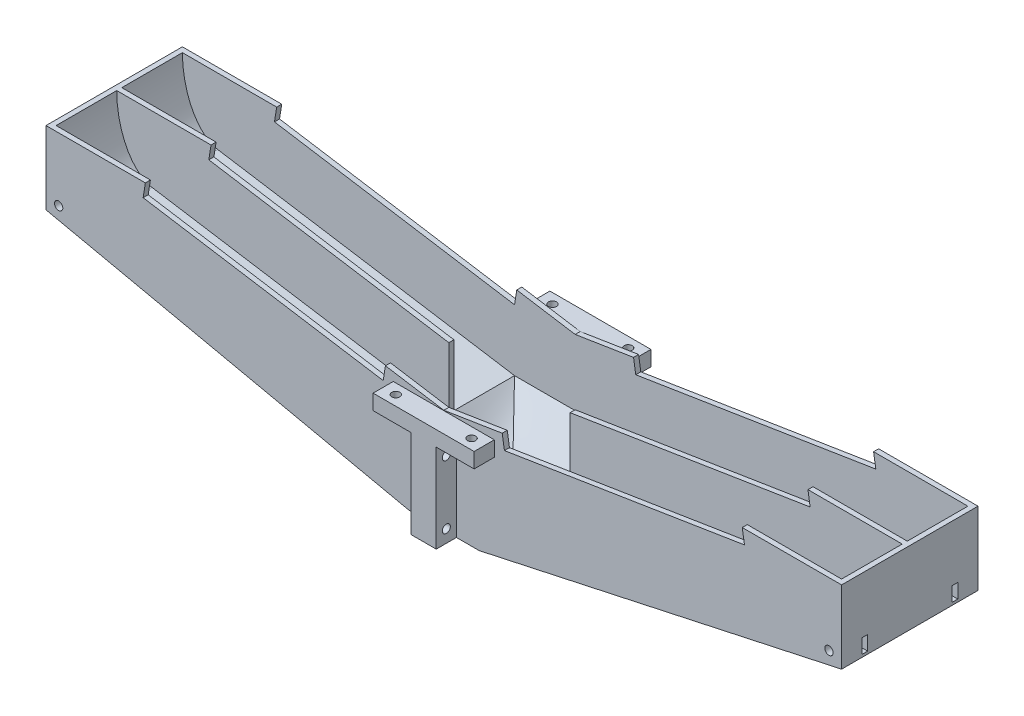
SolidWorks part; units mm, degrees
ref_plane "Front Plane" through (0, 0, 0) normal (0, 0, 1) x (1, 0, 0)
ref_plane "Top Plane" through (0, 0, 0) normal (0, 1, 0) x (1, 0, 0)
ref_plane "Right Plane" through (0, 0, 0) normal (1, 0, 0) x (0, 0, -1)
sketch "Sketch1" plane through (0, 0, 0) normal (0, 1, 0) x (1, 0, 0)
  line L1 (-157.5, -27) -> (157.5, -27)
  line L2 (-157.5, -27) -> (-157.5, 27)
  line L3 (-157.5, 27) -> (157.5, 27)
  line L4 (157.5, -27) -> (157.5, 27)
  line L5 (-157.5, -27) -> (157.5, 27) construction
  line L6 (-157.5, 27) -> (157.5, -27) construction
  point P0 (0, 0)
  dimension "D2" = 315
  dimension "D1" = 54
extrude "Boss-Extrude2" add sketch "Sketch1" along normal blind 60
sketch "Sketch7" plane through (0, 0, 0) normal (0, 0, 1) x (1, 0, 0)
  line L0 (-155.5, 60) -> (-155.5, 36) construction
  line L1 (-141.5, 33.7643) -> (-24, 15)
  line L2 (-157.5, 60) -> (157.5, 60) construction
  line L3 (141.5, 33.7643) -> (24, 15)
  line L4 (-155.5, 36) -> (0, 11.1673) construction
  line L5 (0, 11.1673) -> (155.5, 36) construction
  line L6 (155.5, 36) -> (155.5, 60) construction
  line L7 (155.5, 60) -> (-155.5, 60)
  line L8 (-157.5, 60) -> (-157.5, 0) construction
  line L9 (157.5, 60) -> (157.5, 0) construction
  line L10 (0, 60) -> (0, 0) construction
  line L12 (-24, 15) -> (24, 15)
  line L13 (-157.5, 0) -> (157.5, 0) construction
  ellipse E0 centre (-140.0618, 60) end of major axis (-140.0618, 33.6497) minor radius 15.4382 (-141.5, 33.7643) -> (-155.5, 60) cw
  ellipse E1 centre (140.0618, 60) end of major axis (140.0618, 86.3503) minor radius 15.4382 (155.5, 60) -> (141.5, 33.7643) cw
  dimension "D1" = 2
  dimension "D2" = 2
  dimension "D3" = 24
  dimension "D4" = 15
  dimension "D5" = 48
  dimension "D6" = 16
extrude "Cut-Extrude2" cut sketch "Sketch7" along normal offset from surface 2 and the other way offset from surface 2 up to face at (0, 30, 27) other way up to face at (0, 30, -27)
extrude "Boss-Extrude3" add sketch "Sketch7<2>" along normal mid plane 2
sketch "Sketch7<2>" plane through (0, 0, 0) normal (0, 0, 1) x (1, 0, 0) same geometry as "Sketch7"
sketch "Sketch9" plane through (0, 15, 0) normal (0, 1, 0) x (1, 0, 0)
  line L1 (-24, -25) -> (24, -25)
  line L2 (-24, -25) -> (-24, 25)
  line L3 (-24, 25) -> (24, 25)
  line L4 (24, -25) -> (24, 25)
  line L5 (-24, -25) -> (24, 25) construction
  line L6 (-24, 25) -> (24, -25) construction
  point P0 (0, 0)
extrude "Cut-Extrude5" cut sketch "Sketch9" along normal through all
sketch "Sketch10" plane through (0, 0, 0) normal (0, -1, 0) x (1, 0, 0)
  circle A0 centre (0, 0) radius 12
  dimension "D1" = 24
extrude "Cut-Extrude6" cut sketch "Sketch10" against normal blind 2
sketch "Sketch4" plane through (0, 2, 0) normal (0, -1, 0) x (1, 0, 0)
  circle A0 centre (0, 0) radius 12
  dimension "D1" = 24
loft "Cut-Loft3" cut profiles "Sketch4", "Sketch9<2>" connector at (0, 2, -12) connector at (-24, 15, -25)
sketch "Sketch9<2>" plane through (0, 15, 0) normal (0, 1, 0) x (1, 0, 0) same geometry as "Sketch9"
sketch "Sketch11" plane through (0, 0, 27) normal (0, 0, 1) x (1, 0, 0)
  line L0 (-157.5, 31.0917) -> (-14, 0)
  line L1 (-157.5, 60) -> (-157.5, 0) construction
  line L2 (-157.5, 0) -> (157.5, 0) construction
  line L3 (-14, 0) -> (-157.5, 0)
  line L4 (-157.5, 0) -> (-157.5, 31.0917)
  line L5 (157.5, 31.0917) -> (157.5, 0)
  line L6 (157.5, 60) -> (157.5, 0) construction
  line L7 (157.5, 0) -> (14, 0)
  line L8 (14, 0) -> (157.5, 31.0917)
  line L9 (-118.1608, 60) -> (-119.042, 54.4819)
  line L10 (-24, 60) -> (-155.5, 60) construction
  line L11 (-119.042, 54.4819) -> (-24, 39.3041)
  line L12 (-118.1608, 60) -> (118.1608, 60)
  line L13 (155.5, 60) -> (24, 60) construction
  line L14 (-141.5, 33.7643) -> (-24, 15) construction
  line L15 (0, 60) -> (0, 0) construction
  line L16 (-141.5, 33.7643) -> (-24, 15) construction
  line L17 (118.1608, 60) -> (119.042, 54.4819)
  line L18 (119.042, 54.4819) -> (24, 39.3041)
  line L19 (-24, 39.3041) -> (-23.1188, 44.8222)
  line L20 (-23.1188, 44.8222) -> (0, 41.1302)
  line L21 (0, 41.1302) -> (23.1188, 44.8222)
  line L22 (23.1188, 44.8222) -> (24, 39.3041)
  line L23 (-24, 60) -> (-24, 15) construction
  line L24 (-12, 0) -> (12, 0) construction
  line L25 (-12, 0) -> (12, 0) construction
  line L26 (-141.5, 33.7643) -> (-142.7705, 27.9003) construction
  line L27 (-152.5, 35) -> (152.5, 35) construction
  line L28 (-157.5, 60) -> (-157.5, 0) construction
  circle A0 centre (-152.5, 35) radius 1.65
  circle A1 centre (152.5, 35) radius 1.65
  point P45 (0, 35)
  dimension "D5" = 3.3
  dimension "D1" = 6
  dimension "D2" = 2
  dimension "D3" = 24
  dimension "D4" = 5.588
  dimension "D6" = 25
  dimension "D7" = 5
extrude "Cut-Extrude7" cut sketch "Sketch11" against normal through all
ref_plane "Plane1" through (0, 0, 19) normal (0, 0, 1) x (1, 0, 0)
sketch "Sketch12" plane through (0, 0, 19) normal (0, 0, 1) x (1, 0, 0)
  line L0 (-157.5, 60) -> (-157.5, 31.0917) construction
  line L1 (-150.8546, 37.85) -> (-157.5, 37.85)
  line L2 (-157.5, 37.85) -> (-157.5, 32.15)
  line L3 (157.5, 37.85) -> (157.5, 32.15)
  line L4 (-157.5, 32.15) -> (-150.8546, 32.15)
  line L5 (-150.8546, 32.15) -> (-149.2091, 35)
  line L6 (-149.2091, 35) -> (-150.8546, 37.85)
  line L7 (150.8546, 37.85) -> (149.2091, 35)
  line L8 (149.2091, 35) -> (150.8546, 32.15)
  line L9 (150.8546, 32.15) -> (157.5, 32.15)
  line L10 (157.5, 60) -> (157.5, 31.0917) construction
  line L12 (157.5, 37.85) -> (150.8546, 37.85)
  line L13 (-153.7857, 38.4731) -> (-155.104, 36.1897) [skipped]
  line L14 (-156.1507, 35.6231) -> (-154.8323, 33.3397) [skipped]
  line L15 (156.3932, 33.9568) -> (154.9682, 36.425) [skipped]
  line L16 (154.1454, 32.15) -> (154.9682, 33.575) [skipped]
  circle A0 centre (-152.5, 35) radius 2.85 construction
  circle A1 centre (152.5, 35) radius 2.85 construction
  dimension "D1" = 5.7
extrude "Cut-Extrude8" cut sketch "Sketch12" against normal blind 2.3
ref_plane "Plane2" through (0, 0, -19) normal (0, 0, -1) x (-1, 0, 0)
sketch "Sketch13" plane through (0, 0, -19) normal (0, 0, -1) x (-1, 0, 0)
  line L1 (-150.8546, 37.85) -> (-157.5, 37.85)
  line L2 (-157.5, 37.85) -> (-157.5, 32.15)
  line L3 (157.5, 37.85) -> (157.5, 32.15)
  line L4 (-157.5, 32.15) -> (-150.8546, 32.15)
  line L5 (-150.8546, 32.15) -> (-149.2091, 35)
  line L6 (-149.2091, 35) -> (-150.8546, 37.85)
  line L7 (150.8546, 37.85) -> (149.2091, 35)
  line L8 (149.2091, 35) -> (150.8546, 32.15)
  line L9 (150.8546, 32.15) -> (157.5, 32.15)
  line L11 (157.5, 60) -> (157.5, 31.0917) construction
  line L12 (157.5, 37.85) -> (150.8546, 37.85)
  line L13 (-153.7857, 38.4731) -> (-155.104, 36.1897) [skipped]
  line L14 (-156.1507, 35.6231) -> (-154.8323, 33.3397) [skipped]
  line L15 (156.3932, 33.9568) -> (154.9682, 36.425) [skipped]
  line L16 (154.1454, 32.15) -> (154.9682, 33.575) [skipped]
  line L17 (-157.5, 60) -> (-157.5, 31.0917) construction
  circle A0 centre (-152.5, 35) radius 2.85 construction
  circle A1 centre (152.5, 35) radius 2.85 construction
  circle A3 centre (-152.5, 35) radius 1.65 construction
  circle A4 centre (-152.5, 35) radius 1.65 construction
  circle A5 centre (152.5, 35) radius 1.65 construction
  circle A6 centre (152.5, 35) radius 1.65 construction
  dimension "D1" = 5.7
extrude "Cut-Extrude9" cut sketch "Sketch13" against normal blind 2.3
ref_plane "Plane3" through (0, 35, 0) normal (0, 1, 0) x (1, 0, 0)
sketch "Sketch14" plane through (0, 35, 0) normal (0, 1, 0) x (1, 0, 0)
  line L0 (-23.1188, 27) -> (0, 27) construction
  line L1 (-20, 27) -> (20, 27)
  line L2 (-20, 27) -> (-20, 35)
  line L3 (-20, 35) -> (20, 35)
  line L4 (20, 27) -> (20, 35)
  line L5 (-23.1188, -27) -> (0, -27) construction
  line L6 (-20, -27) -> (20, -27)
  line L7 (-20, -27) -> (-20, -35)
  line L8 (-20, -35) -> (20, -35)
  line L9 (20, -27) -> (20, -35)
  line L10 (0, 35) -> (0, -35) construction
  point P12 (0, 0)
  point P17 (0, 0)
  point P18 (0, 35)
  point P19 (-14, -27)
  dimension "D1" = 8
  dimension "D2" = 40
extrude "Boss-Extrude4" add sketch "Sketch14" along normal blind 6
sketch "Sketch15" plane through (0, 0, 0) normal (0, 1, 0) x (1, 0, 0)
  line L0 (-20, 27) -> (20, 27) construction
  line L1 (-5, 27) -> (5, 27)
  line L2 (-5, 27) -> (-5, 35)
  line L3 (-5, 35) -> (5, 35)
  line L4 (5, 27) -> (5, 35)
  line L5 (20, 35) -> (-20, 35) construction
  line L6 (-20, -35) -> (20, -35) construction
  line L7 (-5, -35) -> (5, -35)
  line L8 (-5, -35) -> (-5, -27)
  line L9 (-5, -27) -> (5, -27)
  line L10 (5, -35) -> (5, -27)
  line L11 (20, -27) -> (-20, -27) construction
  line L12 (0, 27) -> (0, -27) construction
  point P16 (0, -27)
  point P21 (0, 0)
  point P22 (0, 27)
  dimension "D1" = 10
extrude "Boss-Extrude5" add sketch "Sketch15" along normal up to surface (35 mm away) up to face at (0, 35, 31)
sketch "Sketch16" plane through (-5, 0, 0) normal (-1, 0, 0) x (0, 0, 1)
  line L0 (-27, 17.5) -> (-35, 17.5) construction
  line L1 (-27, 35) -> (-27, 0) construction
  line L2 (-35, 35) -> (-35, 0) construction
  line L3 (27, 17.5) -> (35, 17.5) construction
  line L5 (27, 35) -> (27, 0) construction
  line L6 (35, 35) -> (35, 0) construction
  line L7 (-31, 30) -> (-31, 5) construction
  line L8 (31, 30) -> (31, 5) construction
  circle A0 centre (-31, 30) radius 1.6
  circle A1 centre (-31, 5) radius 1.6
  circle A2 centre (31, 30) radius 1.6
  circle A3 centre (31, 5) radius 1.6
  point P15 (-31, 17.5)
  point P18 (31, 17.5)
  dimension "D1" = 3.2
  dimension "D2" = 25
extrude "Cut-Extrude10" cut sketch "Sketch16" against normal through all
sketch "Sketch17" plane through (0, 41, 0) normal (0, 1, 0) x (1, 0, 0)
  line L0 (-20, 31) -> (20, 31) construction
  line L1 (-20, 35) -> (-20, 27) construction
  line L2 (20, 27) -> (20, 35) construction
  line L3 (-20, -31) -> (20, -31) construction
  line L4 (-20, -27) -> (-20, -35) construction
  line L5 (20, -35) -> (20, -27) construction
  line L7 (-15, -31) -> (15, -31) construction
  line L8 (-15, -31) -> (-15, 31) construction
  line L9 (-15, 31) -> (15, 31) construction
  line L10 (15, -31) -> (15, 31) construction
  line L11 (-15, -31) -> (15, 31) construction
  line L12 (-15, 31) -> (15, -31) construction
  circle A0 centre (-15, 31) radius 1.6
  circle A1 centre (15, 31) radius 1.6
  circle A2 centre (-15, -31) radius 1.6
  circle A3 centre (15, -31) radius 1.6
  point P12 (0, 0)
  dimension "D1" = 3.2
  dimension "D2" = 30
extrude "Cut-Extrude11" cut sketch "Sketch17" against normal up to surface (6 mm away) up to face at (-12.5, 35, 31)
